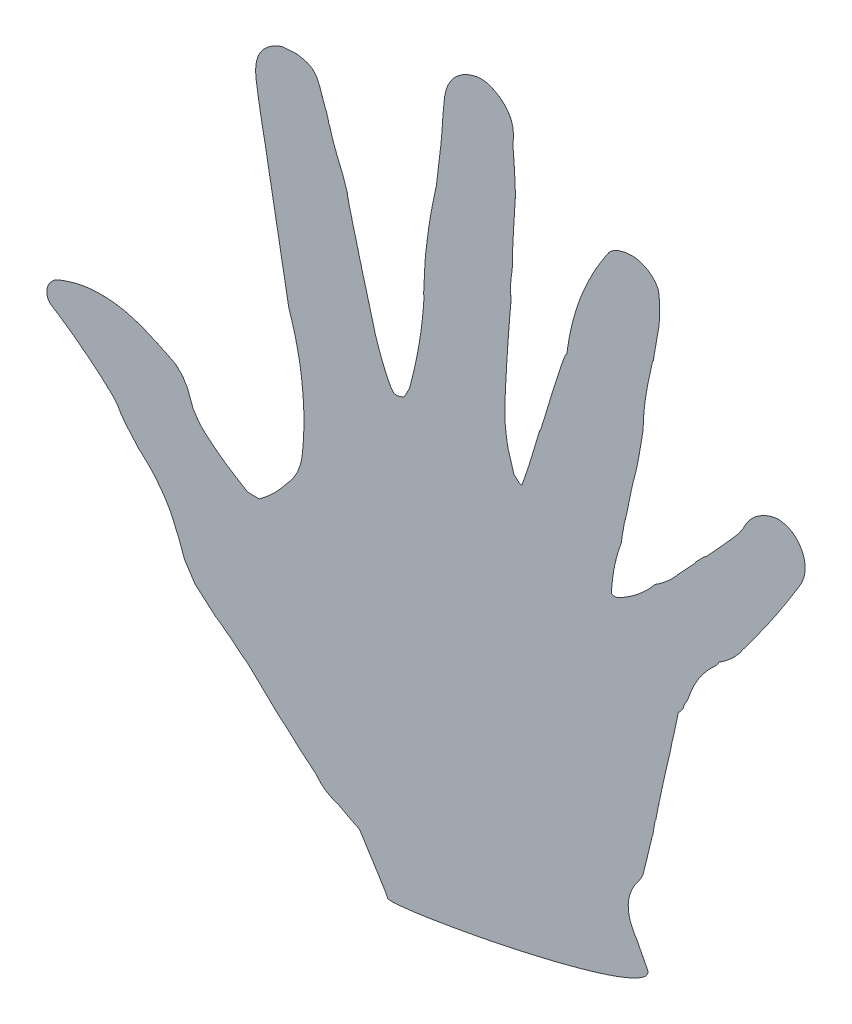
SolidWorks part; units mm, degrees
ref_plane "Plan de face" through (0, 0, 0) normal (0, 0, 1) x (1, 0, 0)
ref_plane "Plan de dessus" through (0, 0, 0) normal (0, 1, 0) x (1, 0, 0)
ref_plane "Plan de droite" through (0, 0, 0) normal (1, 0, 0) x (0, 0, -1)
sketch "Model" plane through (0, 0, 0) normal (0, 0, 1) x (1, 0, 0)
  line L0 (124.2622, -67.0317) -> (124.2391, -67.1279)
  line L1 (124.2391, -67.1279) -> (124.1933, -67.3399)
  line L2 (124.1933, -67.3399) -> (124.1478, -67.4942)
  line L3 (124.1478, -67.4942) -> (124.1478, -67.5328)
  line L4 (124.1478, -67.5328) -> (124.1247, -67.5707)
  line L5 (124.1247, -67.5707) -> (124.1247, -67.5907)
  line L6 (124.1247, -67.5907) -> (124.1023, -67.6102)
  line L7 (124.1023, -67.6102) -> (124.1247, -67.5707)
  line L8 (124.1247, -67.5707) -> (124.1247, -67.5523)
  line L9 (124.1247, -67.5523) -> (124.1478, -67.5137)
  line L10 (124.1478, -67.5137) -> (124.1478, -67.4942)
  line L11 (124.1478, -67.4942) -> (124.1478, -67.4364)
  line L12 (124.1478, -67.4364) -> (124.1933, -67.3399)
  line L13 (124.1933, -67.3399) -> (124.2167, -67.2626)
  line L14 (124.2167, -67.2626) -> (124.2622, -67.0317)
  line L15 (69.8453, -38.7148) -> (69.7992, -38.0785)
  line L16 (69.7992, -38.0785) -> (69.7308, -37.4801)
  line L17 (69.7308, -37.4801) -> (69.7075, -36.8825)
  line L18 (69.7075, -36.8825) -> (69.6846, -36.3227)
  line L19 (69.6846, -36.3227) -> (69.7075, -35.7444)
  line L20 (69.7075, -35.7444) -> (69.7308, -35.2046)
  line L21 (69.7308, -35.2046) -> (69.8453, -34.144)
  line L22 (69.8453, -34.144) -> (70.0743, -33.1213)
  line L23 (70.0743, -33.1213) -> (70.2345, -32.6199)
  line L24 (70.2345, -32.6199) -> (70.3719, -32.1567)
  line L25 (70.3719, -32.1567) -> (70.5781, -31.6746)
  line L26 (70.5781, -31.6746) -> (70.7841, -31.231)
  line L27 (70.7841, -31.231) -> (71.0134, -30.7874)
  line L28 (71.0134, -30.7874) -> (71.242, -30.3826)
  line L29 (71.242, -30.3826) -> (71.8378, -29.5525)
  line L30 (71.8378, -29.5525) -> (72.1586, -29.1476)
  line L31 (72.1586, -29.1476) -> (72.4791, -28.7814)
  line L32 (72.4791, -28.7814) -> (72.8681, -28.3957)
  line L33 (72.8681, -28.3957) -> (73.2345, -28.0481)
  line L34 (73.2345, -28.0481) -> (73.6467, -27.7008)
  line L35 (73.6467, -27.7008) -> (74.0594, -27.3926)
  line L36 (74.0594, -27.3926) -> (74.5402, -27.0642)
  line L37 (74.5402, -27.0642) -> (74.9984, -26.7748)
  line L38 (74.9984, -26.7748) -> (76.0059, -26.216)
  line L39 (76.0059, -26.216) -> (77.105, -25.6949)
  line L40 (77.105, -25.6949) -> (77.7009, -25.4439)
  line L41 (77.7009, -25.4439) -> (78.2731, -25.2319)
  line L42 (78.2731, -25.2319) -> (83.2661, -24.9425)
  line L43 (83.2661, -24.9425) -> (84.1592, -25.1163)
  line L44 (84.1592, -25.1163) -> (85.0982, -25.3282)
  line L45 (85.0982, -25.3282) -> (85.9915, -25.5602)
  line L46 (85.9915, -25.5602) -> (86.3808, -25.6758)
  line L47 (86.3808, -25.6758) -> (86.7015, -25.8103)
  line L48 (86.7015, -25.8103) -> (87.2737, -26.0425)
  line L49 (87.2737, -26.0425) -> (87.4806, -26.1579)
  line L50 (87.4806, -26.1579) -> (87.6405, -26.2928)
  line L51 (87.6405, -26.2928) -> (88.1672, -26.6015)
  line L52 (88.1672, -26.6015) -> (89.4498, -28.0681)
  line L53 (89.4498, -28.0681) -> (89.9077, -29.0511)
  line L54 (89.9077, -29.0511) -> (90.3891, -30.1315)
  line L55 (90.3891, -30.1315) -> (90.5952, -30.672)
  line L56 (90.5952, -30.672) -> (90.7783, -31.1926)
  line L57 (90.7783, -31.1926) -> (90.9612, -31.6746)
  line L58 (90.9612, -31.6746) -> (91.0988, -32.1376)
  line L59 (91.0988, -32.1376) -> (91.2589, -32.5611)
  line L60 (91.2589, -32.5611) -> (91.3963, -32.9668)
  line L61 (91.3963, -32.9668) -> (91.5341, -33.333)
  line L62 (91.5341, -33.333) -> (91.6256, -33.6806)
  line L63 (91.6256, -33.6806) -> (91.763, -33.9895)
  line L64 (91.763, -33.9895) -> (91.8547, -34.2787)
  line L65 (91.8547, -34.2787) -> (91.9463, -34.5297)
  line L66 (91.9463, -34.5297) -> (92.0147, -34.7607)
  line L67 (92.0147, -34.7607) -> (92.1064, -34.9539)
  line L68 (92.1064, -34.9539) -> (92.1753, -35.1274)
  line L69 (92.1753, -35.1274) -> (92.2209, -35.2618)
  line L70 (92.2209, -35.2618) -> (92.2438, -35.378)
  line L71 (92.2438, -35.378) -> (92.6562, -36.3811)
  line L72 (92.6562, -36.3811) -> (92.9768, -37.4036)
  line L73 (92.9768, -37.4036) -> (93.2515, -38.4445)
  line L74 (93.2515, -38.4445) -> (93.412, -39.5056)
  line L75 (93.412, -39.5056) -> (93.6411, -39.545)
  line L76 (93.6411, -39.545) -> (93.7097, -39.7759)
  line L77 (93.7097, -39.7759) -> (93.7783, -40.0651)
  line L78 (93.7783, -40.0651) -> (93.8702, -40.3732)
  line L79 (93.8702, -40.3732) -> (93.9388, -40.721)
  line L80 (93.9388, -40.721) -> (94.0535, -41.0679)
  line L81 (94.0535, -41.0679) -> (94.1679, -41.4543)
  line L82 (94.1679, -41.4543) -> (94.305, -41.8596)
  line L83 (94.305, -41.8596) -> (94.4196, -42.3218)
  line L84 (94.4196, -42.3218) -> (94.6032, -42.766)
  line L85 (94.6032, -42.766) -> (94.7634, -43.2671)
  line L86 (94.7634, -43.2671) -> (94.9463, -43.7689)
  line L87 (94.9463, -43.7689) -> (95.1299, -44.3275)
  line L88 (95.1299, -44.3275) -> (95.3587, -44.8875)
  line L89 (95.3587, -44.8875) -> (95.5647, -45.4849)
  line L90 (95.5647, -45.4849) -> (95.8169, -46.1033)
  line L91 (95.8169, -46.1033) -> (96.046, -46.7586)
  line L92 (96.046, -46.7586) -> (96.5729, -48.032)
  line L93 (96.5729, -48.032) -> (97.0764, -49.2857)
  line L94 (97.0764, -49.2857) -> (97.5801, -50.462)
  line L95 (97.5801, -50.462) -> (98.0615, -51.6194)
  line L96 (98.0615, -51.6194) -> (99.5727, -56.2298)
  line L97 (99.5727, -56.2298) -> (99.5498, -56.8275)
  line L98 (99.5498, -56.8275) -> (99.6875, -57.3095)
  line L99 (99.6875, -57.3095) -> (99.8249, -57.9076)
  line L100 (99.8249, -57.9076) -> (99.9166, -58.2355)
  line L101 (99.9166, -58.2355) -> (99.9849, -58.6014)
  line L102 (99.9849, -58.6014) -> (100.1687, -59.4124)
  line L103 (100.1687, -59.4124) -> (100.3973, -60.2804)
  line L104 (100.3973, -60.2804) -> (100.5348, -60.7432)
  line L105 (100.5348, -60.7432) -> (100.6493, -61.2638)
  line L106 (100.6493, -61.2638) -> (100.9239, -62.3442)
  line L107 (100.9239, -62.3442) -> (101.1993, -63.5401)
  line L108 (101.1993, -63.5401) -> (101.3823, -64.1385)
  line L109 (101.3823, -64.1385) -> (101.5423, -64.7938)
  line L110 (101.5423, -64.7938) -> (101.909, -66.1636)
  line L111 (101.909, -66.1636) -> (102.1152, -66.8576)
  line L112 (102.1152, -66.8576) -> (102.2981, -67.6102)
  line L113 (102.2981, -67.6102) -> (102.5043, -68.3619)
  line L114 (102.5043, -68.3619) -> (102.6873, -69.1722)
  line L115 (102.6873, -69.1722) -> (102.9165, -69.963)
  line L116 (102.9165, -69.963) -> (103.1226, -70.8115)
  line L117 (103.1226, -70.8115) -> (103.5809, -72.5671)
  line L118 (103.5809, -72.5671) -> (103.8331, -73.4541)
  line L119 (103.8331, -73.4541) -> (104.0617, -74.3998)
  line L120 (104.0617, -74.3998) -> (104.5659, -76.3473)
  line L121 (104.5659, -76.3473) -> (105.642, -80.2444)
  line L122 (105.642, -80.2444) -> (106.6726, -84.0629)
  line L123 (106.6726, -84.0629) -> (107.1766, -85.9346)
  line L124 (107.1766, -85.9346) -> (107.6804, -87.7859)
  line L125 (107.6804, -87.7859) -> (108.665, -91.4509)
  line L126 (108.665, -91.4509) -> (109.5125, -93.9584)
  line L127 (109.5125, -93.9584) -> (110.4291, -96.4661)
  line L128 (110.4291, -96.4661) -> (110.9328, -97.701)
  line L129 (110.9328, -97.701) -> (111.4364, -98.9547)
  line L130 (111.4364, -98.9547) -> (111.9863, -100.1891)
  line L131 (111.9863, -100.1891) -> (112.2608, -100.8059)
  line L132 (112.2608, -100.8059) -> (112.3987, -101.1146)
  line L133 (112.3987, -101.1146) -> (112.4669, -101.2693)
  line L134 (112.4669, -101.2693) -> (112.513, -101.4429)
  line L135 (112.513, -101.4429) -> (113.6813, -103.5065)
  line L136 (113.6813, -103.5065) -> (113.9787, -103.8924)
  line L137 (113.9787, -103.8924) -> (114.208, -104.2012)
  line L138 (114.208, -104.2012) -> (114.3227, -104.3161)
  line L139 (114.3227, -104.3161) -> (114.414, -104.4124)
  line L140 (114.414, -104.4124) -> (114.5057, -104.4904)
  line L141 (114.5057, -104.4904) -> (114.5511, -104.5488)
  line L142 (114.5511, -104.5488) -> (114.7801, -104.6253)
  line L143 (114.7801, -104.6253) -> (114.8493, -104.6253)
  line L144 (114.8493, -104.6253) -> (114.8948, -104.6453)
  line L145 (114.8948, -104.6453) -> (114.9864, -104.6832)
  line L146 (114.9864, -104.6832) -> (115.1239, -104.6832)
  line L147 (115.1239, -104.6832) -> (115.1925, -104.6832)
  line L148 (115.1925, -104.6832) -> (115.2386, -104.7023)
  line L149 (115.2386, -104.7023) -> (115.3757, -104.7023)
  line L150 (115.3757, -104.7023) -> (115.4446, -104.7023)
  line L151 (115.4446, -104.7023) -> (115.4901, -104.7216)
  line L152 (115.4901, -104.7216) -> (115.7883, -104.6832)
  line L153 (115.7883, -104.6832) -> (116.0629, -104.6453)
  line L154 (116.0629, -104.6453) -> (116.3836, -104.5673)
  line L155 (116.3836, -104.5673) -> (116.7042, -104.4708)
  line L156 (116.7042, -104.4708) -> (116.9334, -104.3745)
  line L157 (116.9334, -104.3745) -> (117.1394, -104.2975)
  line L158 (117.1394, -104.2975) -> (117.368, -104.1818)
  line L159 (117.368, -104.1818) -> (117.4373, -104.1432)
  line L160 (117.4373, -104.1432) -> (117.4826, -104.1235)
  line L161 (117.4826, -104.1235) -> (117.5747, -104.0853)
  line L162 (117.5747, -104.0853) -> (117.9179, -103.8924)
  line L163 (117.9179, -103.8924) -> (119.6127, -100.7675)
  line L164 (119.6127, -100.7675) -> (120.5749, -97.1026)
  line L165 (120.5749, -97.1026) -> (121.4224, -93.4763)
  line L166 (121.4224, -93.4763) -> (122.1782, -89.8495)
  line L167 (122.1782, -89.8495) -> (122.819, -86.2812)
  line L168 (122.819, -86.2812) -> (123.3689, -82.713)
  line L169 (123.3689, -82.713) -> (123.8042, -79.1835)
  line L170 (123.8042, -79.1835) -> (124.1478, -75.672)
  line L171 (124.1478, -75.672) -> (124.3767, -72.2004)
  line L172 (124.3767, -72.2004) -> (124.2167, -71.9691)
  line L173 (124.2167, -71.9691) -> (124.6749, -62.652)
  line L174 (124.6749, -62.652) -> (124.9261, -59.9135)
  line L175 (124.9261, -59.9135) -> (125.2242, -57.387)
  line L176 (125.2242, -57.387) -> (125.5448, -54.8795)
  line L177 (125.5448, -54.8795) -> (125.8879, -52.3722)
  line L178 (125.8879, -52.3722) -> (126.2776, -49.8831)
  line L179 (126.2776, -49.8831) -> (126.7127, -47.3756)
  line L180 (126.7127, -47.3756) -> (127.1943, -44.8875)
  line L181 (127.1943, -44.8875) -> (127.6976, -42.399)
  line L182 (127.6976, -42.399) -> (128.2247, -39.9306)
  line L183 (128.2247, -39.9306) -> (128.2706, -39.8722)
  line L184 (128.2706, -39.8722) -> (128.2706, -39.8143)
  line L185 (128.2706, -39.8143) -> (128.2929, -39.7759)
  line L186 (128.2929, -39.7759) -> (128.2929, -39.7567)
  line L187 (128.2929, -39.7567) -> (128.2929, -39.718)
  line L188 (128.2929, -39.718) -> (128.2929, -39.6021)
  line L189 (128.2929, -39.6021) -> (128.3395, -39.4486)
  line L190 (128.3395, -39.4486) -> (128.3618, -39.409)
  line L191 (128.3618, -39.409) -> (128.3618, -39.3902)
  line L192 (128.3618, -39.3902) -> (128.3618, -39.3521)
  line L193 (128.3618, -39.3521) -> (128.3618, -39.2743)
  line L194 (128.3618, -39.2743) -> (128.4073, -39.0624)
  line L195 (128.4073, -39.0624) -> (128.4073, -38.8302)
  line L196 (128.4073, -38.8302) -> (128.522, -37.9625)
  line L197 (128.522, -37.9625) -> (128.6137, -37.1908)
  line L198 (128.6137, -37.1908) -> (128.6595, -36.8446)
  line L199 (128.6595, -36.8446) -> (128.705, -36.4775)
  line L200 (128.705, -36.4775) -> (128.797, -35.7062)
  line L201 (128.797, -35.7062) -> (128.8424, -35.4745)
  line L202 (128.8424, -35.4745) -> (128.8659, -35.3584)
  line L203 (128.8659, -35.3584) -> (128.8659, -35.2618)
  line L204 (128.8659, -35.2618) -> (128.9117, -34.8189)
  line L205 (128.9117, -34.8189) -> (129.0033, -33.8928)
  line L206 (129.0033, -33.8928) -> (129.1408, -32.8509)
  line L207 (129.1408, -32.8509) -> (129.2093, -32.3114)
  line L208 (129.2093, -32.3114) -> (129.2555, -31.7517)
  line L209 (129.2555, -31.7517) -> (129.3465, -31.154)
  line L210 (129.3465, -31.154) -> (129.3926, -30.8453)
  line L211 (129.3926, -30.8453) -> (129.4154, -30.691)
  line L212 (129.4154, -30.691) -> (129.4154, -30.5556)
  line L213 (129.4154, -30.5556) -> (129.5525, -29.2825)
  line L214 (129.5525, -29.2825) -> (129.7137, -28.1061)
  line L215 (129.7137, -28.1061) -> (129.8284, -26.9875)
  line L216 (129.8284, -26.9875) -> (129.9421, -25.9266)
  line L217 (129.9421, -25.9266) -> (130.0338, -24.9234)
  line L218 (130.0338, -24.9234) -> (130.1254, -23.9395)
  line L219 (130.1254, -23.9395) -> (130.1936, -23.0334)
  line L220 (130.1936, -23.0334) -> (130.2628, -22.1652)
  line L221 (130.2628, -22.1652) -> (130.2859, -21.3551)
  line L222 (130.2859, -21.3551) -> (130.4461, -19.1756)
  line L223 (130.4461, -19.1756) -> (130.6294, -17.0152)
  line L224 (130.6294, -17.0152) -> (130.8354, -14.8551)
  line L225 (130.8354, -14.8551) -> (131.0876, -12.7136)
  line L226 (131.0876, -12.7136) -> (131.3167, -11.6329)
  line L227 (131.3167, -11.6329) -> (131.5913, -10.5723)
  line L228 (131.5913, -10.5723) -> (131.7749, -10.0326)
  line L229 (131.7749, -10.0326) -> (131.9802, -9.5307)
  line L230 (131.9802, -9.5307) -> (132.4384, -8.5278)
  line L231 (132.4384, -8.5278) -> (132.7819, -7.9299)
  line L232 (132.7819, -7.9299) -> (133.1488, -7.3704)
  line L233 (133.1488, -7.3704) -> (133.5378, -6.8302)
  line L234 (133.5378, -6.8302) -> (133.9271, -6.3483)
  line L235 (133.9271, -6.3483) -> (134.3849, -5.8463)
  line L236 (134.3849, -5.8463) -> (134.8434, -5.4038)
  line L237 (134.8434, -5.4038) -> (135.3247, -4.9783)
  line L238 (135.3247, -4.9783) -> (135.8053, -4.5925)
  line L239 (135.8053, -4.5925) -> (136.3552, -4.188)
  line L240 (136.3552, -4.188) -> (136.9043, -3.8408)
  line L241 (136.9043, -3.8408) -> (137.4769, -3.5126)
  line L242 (137.4769, -3.5126) -> (138.0729, -3.2234)
  line L243 (138.0729, -3.2234) -> (138.714, -2.934)
  line L244 (138.714, -2.934) -> (139.3782, -2.7032)
  line L245 (139.3782, -2.7032) -> (140.0652, -2.4707)
  line L246 (140.0652, -2.4707) -> (140.7518, -2.2977)
  line L247 (140.7518, -2.2977) -> (141.4846, -2.1244)
  line L248 (141.4846, -2.1244) -> (142.1949, -2.028)
  line L249 (142.1949, -2.028) -> (142.905, -1.9885)
  line L250 (142.905, -1.9885) -> (143.5919, -2.028)
  line L251 (143.5919, -2.028) -> (144.2792, -2.0848)
  line L252 (144.2792, -2.0848) -> (144.9434, -2.2397)
  line L253 (144.9434, -2.2397) -> (145.6073, -2.4324)
  line L254 (145.6073, -2.4324) -> (146.2488, -2.7032)
  line L255 (146.2488, -2.7032) -> (147.2792, -3.1654)
  line L256 (147.2792, -3.1654) -> (148.1953, -3.6863)
  line L257 (148.1953, -3.6863) -> (149.0428, -4.2463)
  line L258 (149.0428, -4.2463) -> (149.799, -4.8436)
  line L259 (149.799, -4.8436) -> (150.5086, -5.4801)
  line L260 (150.5086, -5.4801) -> (151.1274, -6.1554)
  line L261 (151.1274, -6.1554) -> (151.6765, -6.869)
  line L262 (151.6765, -6.869) -> (152.1347, -7.6602)
  line L263 (152.1347, -7.6602) -> (152.5468, -8.4505)
  line L264 (152.5468, -8.4505) -> (152.7307, -8.856)
  line L265 (152.7307, -8.856) -> (152.8678, -9.2995)
  line L266 (152.8678, -9.2995) -> (153.1193, -10.1677)
  line L267 (153.1193, -10.1677) -> (153.2568, -11.1127)
  line L268 (153.2568, -11.1127) -> (153.3712, -12.0582)
  line L269 (153.3712, -12.0582) -> (153.3712, -13.0795)
  line L270 (153.3712, -13.0795) -> (153.3712, -13.5813)
  line L271 (153.3712, -13.5813) -> (153.3254, -14.1218)
  line L272 (153.3254, -14.1218) -> (153.1655, -15.2211)
  line L273 (153.1655, -15.2211) -> (153.4401, -18.191)
  line L274 (153.4401, -18.191) -> (153.6468, -21.162)
  line L275 (153.6468, -21.162) -> (153.8297, -24.0938)
  line L276 (153.8297, -24.0938) -> (153.9437, -27.007)
  line L277 (153.9437, -27.007) -> (154.0126, -28.4341)
  line L278 (154.0126, -28.4341) -> (153.9903, -29.8809)
  line L279 (153.9903, -29.8809) -> (153.9214, -31.3275)
  line L280 (153.9214, -31.3275) -> (153.8066, -32.794)
  line L281 (153.8066, -32.794) -> (153.7153, -34.3171)
  line L282 (153.7153, -34.3171) -> (153.623, -35.9182)
  line L283 (153.623, -35.9182) -> (153.5321, -37.5763)
  line L284 (153.5321, -37.5763) -> (153.3943, -39.3321)
  line L285 (153.3943, -39.3321) -> (153.3712, -40.1805)
  line L286 (153.3712, -40.1805) -> (153.3254, -41.0108)
  line L287 (153.3254, -41.0108) -> (153.2802, -41.8202)
  line L288 (153.2802, -41.8202) -> (153.2337, -42.6115)
  line L289 (153.2337, -42.6115) -> (153.211, -43.3445)
  line L290 (153.211, -43.3445) -> (153.1655, -44.0776)
  line L291 (153.1655, -44.0776) -> (153.1424, -44.7716)
  line L292 (153.1424, -44.7716) -> (153.0963, -45.447)
  line L293 (153.0963, -45.447) -> (153.0963, -46.064)
  line L294 (153.0963, -46.064) -> (153.0745, -46.6816)
  line L295 (153.0745, -46.6816) -> (153.0745, -47.2605)
  line L296 (153.0745, -47.2605) -> (153.0277, -47.8195)
  line L297 (153.0277, -47.8195) -> (153.0277, -48.34)
  line L298 (153.0277, -48.34) -> (153.0277, -48.8415)
  line L299 (153.0277, -48.8415) -> (153.0277, -49.3047)
  line L300 (153.0277, -49.3047) -> (153.0277, -49.517)
  line L301 (153.0277, -49.517) -> (153.0046, -49.7482)
  line L302 (153.0046, -49.7482) -> (153.0046, -49.8831)
  line L303 (153.0046, -49.8831) -> (153.0046, -50.0953)
  line L304 (153.0046, -50.0953) -> (152.9822, -50.3657)
  line L305 (152.9822, -50.3657) -> (152.9364, -50.7323)
  line L306 (152.9364, -50.7323) -> (152.8902, -51.1183)
  line L307 (152.8902, -51.1183) -> (152.8451, -51.6005)
  line L308 (152.8451, -51.6005) -> (152.7762, -52.121)
  line L309 (152.7762, -52.121) -> (152.6842, -52.7379)
  line L310 (152.6842, -52.7379) -> (152.6387, -53.3365)
  line L311 (152.6387, -53.3365) -> (152.616, -53.606)
  line L312 (152.616, -53.606) -> (152.5702, -53.8758)
  line L313 (152.5702, -53.8758) -> (152.5237, -54.3579)
  line L314 (152.5237, -54.3579) -> (152.5237, -54.4544)
  line L315 (152.5237, -54.4544) -> (152.5016, -54.5705)
  line L316 (152.5016, -54.5705) -> (152.4555, -54.802)
  line L317 (152.4555, -54.802) -> (152.4555, -54.9761)
  line L318 (152.4555, -54.9761) -> (152.4327, -55.1689)
  line L319 (152.4327, -55.1689) -> (152.3869, -55.4772)
  line L320 (152.3869, -55.4772) -> (152.3869, -55.728)
  line L321 (152.3869, -55.728) -> (152.3869, -55.8245)
  line L322 (152.3869, -55.8245) -> (152.3642, -55.9404)
  line L323 (152.3642, -55.9404) -> (152.3642, -55.9974)
  line L324 (152.3642, -55.9974) -> (152.5016, -57.6182)
  line L325 (152.5016, -57.6182) -> (152.5468, -59.2577)
  line L326 (152.5468, -59.2577) -> (152.5016, -60.8971)
  line L327 (152.5016, -60.8971) -> (152.3411, -62.5555)
  line L328 (152.3411, -62.5555) -> (152.2949, -63.2308)
  line L329 (152.2949, -63.2308) -> (152.2036, -63.9837)
  line L330 (152.2036, -63.9837) -> (152.1578, -64.755)
  line L331 (152.1578, -64.755) -> (152.0662, -65.585)
  line L332 (152.0662, -65.585) -> (152.02, -66.4332)
  line L333 (152.02, -66.4332) -> (151.9291, -67.3399)
  line L334 (151.9291, -67.3399) -> (151.8598, -68.2854)
  line L335 (151.8598, -68.2854) -> (151.7682, -69.2881)
  line L336 (151.7682, -69.2881) -> (151.7227, -70.3104)
  line L337 (151.7227, -70.3104) -> (151.6307, -71.3717)
  line L338 (151.6307, -71.3717) -> (151.5618, -72.4705)
  line L339 (151.5618, -72.4705) -> (151.4709, -73.647)
  line L340 (151.4709, -73.647) -> (151.4243, -74.8239)
  line L341 (151.4243, -74.8239) -> (151.3327, -76.0775)
  line L342 (151.3327, -76.0775) -> (151.2421, -77.3514)
  line L343 (151.2421, -77.3514) -> (151.1501, -78.6817)
  line L344 (151.1501, -78.6817) -> (151.104, -79.9934)
  line L345 (151.104, -79.9934) -> (151.013, -81.2856)
  line L346 (151.013, -81.2856) -> (150.9665, -82.5395)
  line L347 (150.9665, -82.5395) -> (150.8755, -83.7932)
  line L348 (150.8755, -83.7932) -> (150.829, -84.989)
  line L349 (150.829, -84.989) -> (150.806, -85.5681)
  line L350 (150.806, -85.5681) -> (150.7605, -86.166)
  line L351 (150.7605, -86.166) -> (150.7147, -87.3041)
  line L352 (150.7147, -87.3041) -> (150.7147, -87.5745)
  line L353 (150.7147, -87.5745) -> (150.7147, -87.7089)
  line L354 (150.7147, -87.7089) -> (150.6916, -87.8637)
  line L355 (150.6916, -87.8637) -> (150.6461, -88.4421)
  line L356 (150.6461, -88.4421) -> (150.623, -89.2905)
  line L357 (150.623, -89.2905) -> (150.623, -89.7149)
  line L358 (150.623, -89.7149) -> (150.623, -89.9273)
  line L359 (150.623, -89.9273) -> (150.5996, -90.1587)
  line L360 (150.5996, -90.1587) -> (150.5775, -91.8561)
  line L361 (150.5775, -91.8561) -> (150.623, -92.6855)
  line L362 (150.623, -92.6855) -> (150.6461, -93.5345)
  line L363 (150.6461, -93.5345) -> (150.7147, -95.1932)
  line L364 (150.7147, -95.1932) -> (150.8979, -96.8132)
  line L365 (150.8979, -96.8132) -> (151.104, -98.4725)
  line L366 (151.104, -98.4725) -> (151.3789, -100.1312)
  line L367 (151.3789, -100.1312) -> (151.7003, -101.8284)
  line L368 (151.7003, -101.8284) -> (151.8825, -102.3304)
  line L369 (151.8825, -102.3304) -> (153.5548, -107.9242)
  line L370 (153.5548, -107.9242) -> (155.5471, -109.6405)
  line L371 (155.5471, -109.6405) -> (155.7989, -109.66)
  line L372 (155.7989, -109.66) -> (155.9595, -109.6405)
  line L373 (155.9595, -109.6405) -> (156.0738, -109.5826)
  line L374 (156.0738, -109.5826) -> (156.1424, -109.5055)
  line L375 (156.1424, -109.5055) -> (156.3264, -109.0621)
  line L376 (156.3264, -109.0621) -> (156.4862, -108.5994)
  line L377 (156.4862, -108.5994) -> (156.6692, -108.0775)
  line L378 (156.6692, -108.0775) -> (156.8535, -107.5574)
  line L379 (156.8535, -107.5574) -> (157.0819, -106.9787)
  line L380 (157.0819, -106.9787) -> (157.2652, -106.3811)
  line L381 (157.2652, -106.3811) -> (157.4943, -105.7443)
  line L382 (157.4943, -105.7443) -> (157.7006, -105.0878)
  line L383 (157.7006, -105.0878) -> (157.8374, -104.7216)
  line L384 (157.8374, -104.7216) -> (157.9518, -104.3745)
  line L385 (157.9518, -104.3745) -> (158.1812, -103.6223)
  line L386 (158.1812, -103.6223) -> (158.4561, -102.8314)
  line L387 (158.4561, -102.8314) -> (158.6852, -102.0413)
  line L388 (158.6852, -102.0413) -> (158.9598, -101.1919)
  line L389 (158.9598, -101.1919) -> (159.2347, -100.3238)
  line L390 (159.2347, -100.3238) -> (159.5093, -99.4172)
  line L391 (159.5093, -99.4172) -> (159.7842, -98.4725)
  line L392 (159.7842, -98.4725) -> (161.8919, -91.4318)
  line L393 (161.8919, -91.4318) -> (162.1203, -91.3353)
  line L394 (162.1203, -91.3353) -> (162.7846, -89.2138)
  line L395 (162.7846, -89.2138) -> (163.4026, -87.2269)
  line L396 (163.4026, -87.2269) -> (163.9986, -85.3168)
  line L397 (163.9986, -85.3168) -> (164.5254, -83.5234)
  line L398 (164.5254, -83.5234) -> (165.0514, -81.8065)
  line L399 (165.0514, -81.8065) -> (165.5327, -80.2246)
  line L400 (165.5327, -80.2246) -> (165.9909, -78.7201)
  line L401 (165.9909, -78.7201) -> (166.4033, -77.3314)
  line L402 (166.4033, -77.3314) -> (166.8163, -76.0775)
  line L403 (166.8163, -76.0775) -> (167.1815, -74.9201)
  line L404 (167.1815, -74.9201) -> (167.5484, -73.8208)
  line L405 (167.5484, -73.8208) -> (167.8695, -72.7987)
  line L406 (167.8695, -72.7987) -> (168.1896, -71.8146)
  line L407 (168.1896, -71.8146) -> (168.4876, -70.9275)
  line L408 (168.4876, -70.9275) -> (168.7625, -70.0982)
  line L409 (168.7625, -70.0982) -> (169.014, -69.3465)
  line L410 (169.014, -69.3465) -> (169.2658, -68.6316)
  line L411 (169.2658, -68.6316) -> (169.4953, -67.9962)
  line L412 (169.4953, -67.9962) -> (169.7013, -67.4172)
  line L413 (169.7013, -67.4172) -> (169.8842, -66.9353)
  line L414 (169.8842, -66.9353) -> (170.0678, -66.4719)
  line L415 (170.0678, -66.4719) -> (170.2277, -66.1052)
  line L416 (170.2277, -66.1052) -> (170.3658, -65.7968)
  line L417 (170.3658, -65.7968) -> (170.4806, -65.585)
  line L418 (170.4806, -65.585) -> (170.7314, -65.4492)
  line L419 (170.7314, -65.4492) -> (171.0752, -63.0382)
  line L420 (171.0752, -63.0382) -> (171.4645, -60.6854)
  line L421 (171.4645, -60.6854) -> (171.9457, -58.332)
  line L422 (171.9457, -58.332) -> (172.4725, -56.0365)
  line L423 (172.4725, -56.0365) -> (173.0909, -53.7409)
  line L424 (173.0909, -53.7409) -> (173.7551, -51.4842)
  line L425 (173.7551, -51.4842) -> (174.5106, -49.2278)
  line L426 (174.5106, -49.2278) -> (175.3126, -47.0283)
  line L427 (175.3126, -47.0283) -> (176.2283, -44.81)
  line L428 (176.2283, -44.81) -> (177.1902, -42.6501)
  line L429 (177.1902, -42.6501) -> (178.221, -40.4897)
  line L430 (178.221, -40.4897) -> (179.2983, -38.3877)
  line L431 (179.2983, -38.3877) -> (180.4651, -36.2844)
  line L432 (180.4651, -36.2844) -> (181.7026, -34.2205)
  line L433 (181.7026, -34.2205) -> (183.0076, -32.1567)
  line L434 (183.0076, -32.1567) -> (184.3584, -30.1506)
  line L435 (184.3584, -30.1506) -> (184.7946, -29.6681)
  line L436 (184.7946, -29.6681) -> (185.2528, -29.2633)
  line L437 (185.2528, -29.2633) -> (185.7561, -28.8969)
  line L438 (185.7561, -28.8969) -> (186.2832, -28.5691)
  line L439 (186.2832, -28.5691) -> (186.8558, -28.2799)
  line L440 (186.8558, -28.2799) -> (187.4738, -28.0288)
  line L441 (187.4738, -28.0288) -> (188.1153, -27.8167)
  line L442 (188.1153, -27.8167) -> (188.7788, -27.6429)
  line L443 (188.7788, -27.6429) -> (189.6725, -27.45)
  line L444 (189.6725, -27.45) -> (190.52, -27.3348)
  line L445 (190.52, -27.3348) -> (191.3671, -27.2767)
  line L446 (191.3671, -27.2767) -> (192.1457, -27.2767)
  line L447 (192.1457, -27.2767) -> (192.9474, -27.3151)
  line L448 (192.9474, -27.3151) -> (193.6798, -27.4312)
  line L449 (193.6798, -27.4312) -> (194.4133, -27.5859)
  line L450 (194.4133, -27.5859) -> (195.1009, -27.8167)
  line L451 (195.1009, -27.8167) -> (195.8103, -28.0681)
  line L452 (195.8103, -28.0681) -> (196.4517, -28.3957)
  line L453 (196.4517, -28.3957) -> (197.0925, -28.7617)
  line L454 (197.0925, -28.7617) -> (197.6882, -29.2055)
  line L455 (197.6882, -29.2055) -> (198.2842, -29.6881)
  line L456 (198.2842, -29.6881) -> (198.8337, -30.2278)
  line L457 (198.8337, -30.2278) -> (199.3832, -30.8255)
  line L458 (199.3832, -30.8255) -> (199.8638, -31.5007)
  line L459 (199.8638, -31.5007) -> (200.3223, -32.2917)
  line L460 (200.3223, -32.2917) -> (200.4598, -32.8319)
  line L461 (200.4598, -32.8319) -> (200.5745, -33.4688)
  line L462 (200.5745, -33.4688) -> (200.6658, -34.144)
  line L463 (200.6658, -34.144) -> (200.7343, -34.9155)
  line L464 (200.7343, -34.9155) -> (200.8032, -35.7251)
  line L465 (200.8032, -35.7251) -> (200.8263, -36.6317)
  line L466 (200.8263, -36.6317) -> (200.8491, -37.5963)
  line L467 (200.8491, -37.5963) -> (200.8263, -38.6374)
  line L468 (200.8263, -38.6374) -> (200.8263, -39.6603)
  line L469 (200.8263, -39.6603) -> (200.7802, -40.6632)
  line L470 (200.7802, -40.6632) -> (200.7343, -41.589)
  line L471 (200.7343, -41.589) -> (200.6658, -42.4953)
  line L472 (200.6658, -42.4953) -> (198.7651, -53.4712)
  line L473 (198.7651, -53.4712) -> (198.5588, -53.5866)
  line L474 (198.5588, -53.5866) -> (198.238, -55.0912)
  line L475 (198.238, -55.0912) -> (197.9173, -56.5571)
  line L476 (197.9173, -56.5571) -> (197.7798, -57.2511)
  line L477 (197.7798, -57.2511) -> (197.7113, -57.5987)
  line L478 (197.7113, -57.5987) -> (197.6203, -57.9658)
  line L479 (197.6203, -57.9658) -> (197.4822, -58.6407)
  line L480 (197.4822, -58.6407) -> (197.4591, -58.7947)
  line L481 (197.4591, -58.7947) -> (197.4136, -58.9685)
  line L482 (197.4136, -58.9685) -> (197.322, -59.3161)
  line L483 (197.322, -59.3161) -> (197.2765, -59.6244)
  line L484 (197.2765, -59.6244) -> (197.2527, -59.7786)
  line L485 (197.2527, -59.7786) -> (197.2076, -59.9514)
  line L486 (197.2076, -59.9514) -> (197.0701, -60.5889)
  line L487 (197.0701, -60.5889) -> (196.8407, -61.8038)
  line L488 (196.8407, -61.8038) -> (196.7491, -62.3826)
  line L489 (196.7491, -62.3826) -> (196.6347, -62.9612)
  line L490 (196.6347, -62.9612) -> (196.543, -63.5202)
  line L491 (196.543, -63.5202) -> (196.4976, -63.7909)
  line L492 (196.4976, -63.7909) -> (196.4976, -63.8488)
  line L493 (196.4976, -63.8488) -> (196.4748, -63.9256)
  line L494 (196.4748, -63.9256) -> (196.4287, -64.08)
  line L495 (196.4287, -64.08) -> (196.2226, -65.4689)
  line L496 (196.2226, -65.4689) -> (196.039, -66.8388)
  line L497 (196.039, -66.8388) -> (195.9708, -67.4942)
  line L498 (195.9708, -67.4942) -> (195.8785, -68.1691)
  line L499 (195.8785, -68.1691) -> (195.7417, -69.4998)
  line L500 (195.7417, -69.4998) -> (195.6501, -70.7731)
  line L501 (195.6501, -70.7731) -> (195.627, -71.3905)
  line L502 (195.627, -71.3905) -> (195.5815, -72.027)
  line L503 (195.5815, -72.027) -> (195.5354, -73.2424)
  line L504 (195.5354, -73.2424) -> (195.5354, -73.8398)
  line L505 (195.5354, -73.8398) -> (195.5126, -74.4576)
  line L506 (195.5126, -74.4576) -> (194.4822, -80.4945)
  line L507 (194.4822, -80.4945) -> (194.3447, -81.3055)
  line L508 (194.3447, -81.3055) -> (194.2069, -82.0959)
  line L509 (194.2069, -82.0959) -> (194.0702, -82.8485)
  line L510 (194.0702, -82.8485) -> (194.0702, -82.925)
  line L511 (194.0702, -82.925) -> (194.0467, -83.022)
  line L512 (194.0467, -83.022) -> (194.0009, -83.2147)
  line L513 (194.0009, -83.2147) -> (193.9093, -83.6002)
  line L514 (193.9093, -83.6002) -> (193.7722, -84.3142)
  line L515 (193.7722, -84.3142) -> (193.6347, -85.0086)
  line L516 (193.6347, -85.0086) -> (193.4976, -85.6644)
  line L517 (193.4976, -85.6644) -> (193.4283, -85.973)
  line L518 (193.4283, -85.973) -> (193.3367, -86.3007)
  line L519 (193.3367, -86.3007) -> (193.2909, -86.5901)
  line L520 (193.2909, -86.5901) -> (193.2223, -86.8991)
  line L521 (193.2223, -86.8991) -> (193.0849, -87.4777)
  line L522 (193.0849, -87.4777) -> (192.8106, -88.5577)
  line L523 (192.8106, -88.5577) -> (192.7186, -89.0592)
  line L524 (192.7186, -89.0592) -> (192.5815, -89.5411)
  line L525 (192.5815, -89.5411) -> (192.5354, -89.753)
  line L526 (192.5354, -89.753) -> (192.4671, -89.9854)
  line L527 (192.4671, -89.9854) -> (192.3287, -90.4286)
  line L528 (192.3287, -90.4286) -> (192.2143, -90.9686)
  line L529 (192.2143, -90.9686) -> (192.0541, -91.5856)
  line L530 (192.0541, -91.5856) -> (191.8942, -92.3)
  line L531 (191.8942, -92.3) -> (191.7106, -93.1099)
  line L532 (191.7106, -93.1099) -> (191.5273, -93.9781)
  line L533 (191.5273, -93.9781) -> (191.322, -94.942)
  line L534 (191.322, -94.942) -> (191.1156, -96.0029)
  line L535 (191.1156, -96.0029) -> (190.8635, -97.1605)
  line L536 (190.8635, -97.1605) -> (190.6802, -98.1833)
  line L537 (190.6802, -98.1833) -> (190.5885, -98.6655)
  line L538 (190.5885, -98.6655) -> (190.4742, -99.1666)
  line L539 (190.4742, -99.1666) -> (190.2912, -100.0926)
  line L540 (190.2912, -100.0926) -> (190.1992, -100.5167)
  line L541 (190.1992, -100.5167) -> (190.1531, -100.7289)
  line L542 (190.1531, -100.7289) -> (190.0845, -100.9602)
  line L543 (190.0845, -100.9602) -> (189.9012, -101.7516)
  line L544 (189.9012, -101.7516) -> (189.7183, -102.5033)
  line L545 (189.7183, -102.5033) -> (189.535, -103.198)
  line L546 (189.535, -103.198) -> (189.4434, -103.5065)
  line L547 (189.4434, -103.5065) -> (189.3976, -103.6607)
  line L548 (189.3976, -103.6607) -> (189.3748, -103.7375)
  line L549 (189.3748, -103.7375) -> (189.329, -103.8341)
  line L550 (189.329, -103.8341) -> (189.2828, -104.2197)
  line L551 (189.2828, -104.2197) -> (189.237, -104.5867)
  line L552 (189.237, -104.5867) -> (189.1916, -104.8951)
  line L553 (189.1916, -104.8951) -> (189.1464, -105.1653)
  line L554 (189.1464, -105.1653) -> (189.1464, -105.3581)
  line L555 (189.1464, -105.3581) -> (189.0996, -105.5317)
  line L556 (189.0996, -105.5317) -> (189.0996, -105.6476)
  line L557 (189.0996, -105.6476) -> (189.0544, -105.7443)
  line L558 (189.0544, -105.7443) -> (189.0083, -105.9176)
  line L559 (189.0083, -105.9176) -> (188.9621, -106.1298)
  line L560 (188.9621, -106.1298) -> (188.9173, -106.3811)
  line L561 (188.9173, -106.3811) -> (188.8481, -106.6701)
  line L562 (188.8481, -106.6701) -> (188.8026, -106.9595)
  line L563 (188.8026, -106.9595) -> (188.7561, -107.3257)
  line L564 (188.7561, -107.3257) -> (188.619, -108.1167)
  line L565 (188.619, -108.1167) -> (188.5277, -108.9267)
  line L566 (188.5277, -108.9267) -> (188.4354, -109.6787)
  line L567 (188.4354, -109.6787) -> (187.7946, -111.5117)
  line L568 (187.7946, -111.5117) -> (187.1993, -113.3819)
  line L569 (187.1993, -113.3819) -> (186.6952, -115.292)
  line L570 (186.6952, -115.292) -> (186.2367, -117.2793)
  line L571 (186.2367, -117.2793) -> (185.8705, -119.2652)
  line L572 (185.8705, -119.2652) -> (185.5728, -121.3103)
  line L573 (185.5728, -121.3103) -> (185.3437, -123.3742)
  line L574 (185.3437, -123.3742) -> (185.1832, -125.5152)
  line L575 (185.1832, -125.5152) -> (185.5039, -125.8235)
  line L576 (185.5039, -125.8235) -> (186.5126, -125.901)
  line L577 (186.5126, -125.901) -> (187.4049, -125.6702)
  line L578 (187.4049, -125.6702) -> (188.2982, -125.1682)
  line L579 (188.2982, -125.1682) -> (189.1464, -124.6856)
  line L580 (189.1464, -124.6856) -> (190.8176, -123.6445)
  line L581 (190.8176, -123.6445) -> (191.642, -123.0848)
  line L582 (191.642, -123.0848) -> (192.4206, -122.5257)
  line L583 (192.4206, -122.5257) -> (193.1992, -121.9276)
  line L584 (193.1992, -121.9276) -> (193.9323, -121.3488)
  line L585 (193.9323, -121.3488) -> (195.421, -120.0759)
  line L586 (195.421, -120.0759) -> (196.8183, -118.7642)
  line L587 (196.8183, -118.7642) -> (197.5059, -118.07)
  line L588 (197.5059, -118.07) -> (198.1467, -117.3756)
  line L589 (198.1467, -117.3756) -> (199.4059, -115.9288)
  line L590 (199.4059, -115.9288) -> (200.5049, -115.2147)
  line L591 (200.5049, -115.2147) -> (201.5364, -114.4628)
  line L592 (201.5364, -114.4628) -> (202.5206, -113.6911)
  line L593 (202.5206, -113.6911) -> (203.4604, -112.8999)
  line L594 (203.4604, -112.8999) -> (204.3989, -112.0516)
  line L595 (204.3989, -112.0516) -> (205.246, -111.1834)
  line L596 (205.246, -111.1834) -> (206.0939, -110.2959)
  line L597 (206.0939, -110.2959) -> (206.8494, -109.3899)
  line L598 (206.8494, -109.3899) -> (212.438, -103.4099)
  line L599 (212.438, -103.4099) -> (212.438, -103.1401)
  line L600 (212.438, -103.1401) -> (215.5066, -100.0347)
  line L601 (215.5066, -100.0347) -> (215.8042, -99.9762)
  line L602 (215.8042, -99.9762) -> (218.3471, -97.2378)
  line L603 (218.3471, -97.2378) -> (220.8664, -94.4792)
  line L604 (220.8664, -94.4792) -> (223.3858, -91.6823)
  line L605 (223.3858, -91.6823) -> (225.8591, -88.8664)
  line L606 (225.8591, -88.8664) -> (226.2939, -88.3264)
  line L607 (226.2939, -88.3264) -> (226.6835, -87.8055)
  line L608 (226.6835, -87.8055) -> (227.0728, -87.2653)
  line L609 (227.0728, -87.2653) -> (227.3942, -86.7253)
  line L610 (227.3942, -86.7253) -> (227.6226, -86.455)
  line L611 (227.6226, -86.455) -> (227.8059, -86.1849)
  line L612 (227.8059, -86.1849) -> (227.9885, -85.8954)
  line L613 (227.9885, -85.8954) -> (228.1263, -85.626)
  line L614 (228.1263, -85.626) -> (228.5153, -84.8737)
  line L615 (228.5153, -84.8737) -> (228.9049, -84.1987)
  line L616 (228.9049, -84.1987) -> (229.3404, -83.5234)
  line L617 (229.3404, -83.5234) -> (229.7751, -82.9055)
  line L618 (229.7751, -82.9055) -> (230.2561, -82.308)
  line L619 (230.2561, -82.308) -> (230.7601, -81.7483)
  line L620 (230.7601, -81.7483) -> (231.3099, -81.2092)
  line L621 (231.3099, -81.2092) -> (231.8597, -80.7267)
  line L622 (231.8597, -80.7267) -> (232.4775, -80.2444)
  line L623 (232.4775, -80.2444) -> (233.0965, -79.8196)
  line L624 (233.0965, -79.8196) -> (233.7604, -79.415)
  line L625 (233.7604, -79.415) -> (234.4243, -79.0479)
  line L626 (234.4243, -79.0479) -> (235.1571, -78.6817)
  line L627 (235.1571, -78.6817) -> (235.8905, -78.3923)
  line L628 (235.8905, -78.3923) -> (236.6691, -78.1032)
  line L629 (236.6691, -78.1032) -> (237.4477, -77.8903)
  line L630 (237.4477, -77.8903) -> (238.3179, -77.6976)
  line L631 (238.3179, -77.6976) -> (239.142, -77.6206)
  line L632 (239.142, -77.6206) -> (239.9667, -77.6404)
  line L633 (239.9667, -77.6404) -> (240.7918, -77.7749)
  line L634 (240.7918, -77.7749) -> (241.5246, -77.9298)
  line L635 (241.5246, -77.9298) -> (242.1885, -78.1415)
  line L636 (242.1885, -78.1415) -> (242.853, -78.3923)
  line L637 (242.853, -78.3923) -> (243.4484, -78.7201)
  line L638 (243.4484, -78.7201) -> (244.0437, -79.0677)
  line L639 (244.0437, -79.0677) -> (244.5708, -79.4728)
  line L640 (244.5708, -79.4728) -> (245.0965, -79.9161)
  line L641 (245.0965, -79.9161) -> (245.555, -80.4178)
  line L642 (245.555, -80.4178) -> (246.3336, -81.3625)
  line L643 (246.3336, -81.3625) -> (246.952, -82.385)
  line L644 (246.952, -82.385) -> (247.3868, -83.2726)
  line L645 (247.3868, -83.2726) -> (247.6851, -84.2178)
  line L646 (247.6851, -84.2178) -> (247.9597, -85.2978)
  line L647 (247.9597, -85.2978) -> (248.0517, -85.8382)
  line L648 (248.0517, -85.8382) -> (248.0741, -86.3971)
  line L649 (248.0741, -86.3971) -> (248.0972, -87.4777)
  line L650 (248.0972, -87.4777) -> (248.0517, -88.0172)
  line L651 (248.0517, -88.0172) -> (247.9597, -88.577)
  line L652 (247.9597, -88.577) -> (247.754, -89.6565)
  line L653 (247.754, -89.6565) -> (247.3868, -90.7369)
  line L654 (247.3868, -90.7369) -> (247.1811, -91.258)
  line L655 (247.1811, -91.258) -> (246.9286, -91.7982)
  line L656 (246.9286, -91.7982) -> (246.3109, -92.8787)
  line L657 (246.3109, -92.8787) -> (243.9748, -96.659)
  line L658 (243.9748, -96.659) -> (242.83, -98.5106)
  line L659 (242.83, -98.5106) -> (241.639, -100.3432)
  line L660 (241.639, -100.3432) -> (239.3032, -103.9306)
  line L661 (239.3032, -103.9306) -> (239.028, -104.3556)
  line L662 (239.028, -104.3556) -> (238.8905, -104.5673)
  line L663 (238.8905, -104.5673) -> (238.7306, -104.7988)
  line L664 (238.7306, -104.7988) -> (238.1343, -105.6862)
  line L665 (238.1343, -105.6862) -> (236.9437, -107.422)
  line L666 (236.9437, -107.422) -> (235.7989, -109.1194)
  line L667 (235.7989, -109.1194) -> (234.6082, -110.7977)
  line L668 (234.6082, -110.7977) -> (232.2718, -114.0768)
  line L669 (232.2718, -114.0768) -> (231.1263, -115.6775)
  line L670 (231.1263, -115.6775) -> (229.936, -117.2597)
  line L671 (229.936, -117.2597) -> (228.7905, -118.822)
  line L672 (228.7905, -118.822) -> (227.5992, -120.3656)
  line L673 (227.5992, -120.3656) -> (227.2554, -120.9821)
  line L674 (227.2554, -120.9821) -> (226.523, -121.8889)
  line L675 (226.523, -121.8889) -> (225.7216, -122.7954)
  line L676 (225.7216, -122.7954) -> (224.9199, -123.6636)
  line L677 (224.9199, -123.6636) -> (224.0266, -124.4927)
  line L678 (224.0266, -124.4927) -> (223.1333, -125.284)
  line L679 (223.1333, -125.284) -> (222.1718, -126.0361)
  line L680 (222.1718, -126.0361) -> (221.1865, -126.7495)
  line L681 (221.1865, -126.7495) -> (220.133, -127.4441)
  line L682 (220.133, -127.4441) -> (219.8815, -127.9071)
  line L683 (219.8815, -127.9071) -> (219.5832, -128.3701)
  line L684 (219.5832, -128.3701) -> (219.2397, -128.7942)
  line L685 (219.2397, -128.7942) -> (218.8052, -129.2186)
  line L686 (218.8052, -129.2186) -> (218.14, -129.8363)
  line L687 (218.14, -129.8363) -> (217.4768, -130.4919)
  line L688 (217.4768, -130.4919) -> (216.1939, -131.8614)
  line L689 (216.1939, -131.8614) -> (215.0487, -133.2694)
  line L690 (215.0487, -133.2694) -> (213.949, -134.7546)
  line L691 (213.949, -134.7546) -> (212.9872, -136.2787)
  line L692 (212.9872, -136.2787) -> (212.1173, -137.8789)
  line L693 (212.1173, -137.8789) -> (211.3383, -139.5184)
  line L694 (211.3383, -139.5184) -> (210.9949, -140.3673)
  line L695 (210.9949, -140.3673) -> (210.6517, -141.2548)
  line L696 (210.6517, -141.2548) -> (210.2618, -142.2776)
  line L697 (210.2618, -142.2776) -> (210.1705, -142.5284)
  line L698 (210.1705, -142.5284) -> (210.1246, -142.6442)
  line L699 (210.1246, -142.6442) -> (210.1246, -142.6628)
  line L700 (210.1246, -142.6628) -> (210.1022, -142.7017)
  line L701 (210.1022, -142.7017) -> (210.0557, -142.7789)
  line L702 (210.0557, -142.7789) -> (209.9641, -143.01)
  line L703 (209.9641, -143.01) -> (209.8494, -143.2416)
  line L704 (209.8494, -143.2416) -> (209.8266, -143.3191)
  line L705 (209.8266, -143.3191) -> (209.7812, -143.4155)
  line L706 (209.7812, -143.4155) -> (209.6895, -143.5888)
  line L707 (209.6895, -143.5888) -> (209.5062, -143.8978)
  line L708 (209.5062, -143.8978) -> (209.3457, -144.1676)
  line L709 (209.3457, -144.1676) -> (209.2771, -144.2834)
  line L710 (209.2771, -144.2834) -> (209.1862, -144.4184)
  line L711 (209.1862, -144.4184) -> (209.048, -144.6499)
  line L712 (209.048, -144.6499) -> (209.0022, -144.746)
  line L713 (209.0022, -144.746) -> (208.9337, -144.8621)
  line L714 (208.9337, -144.8621) -> (208.7728, -145.2862)
  line L715 (208.7728, -145.2862) -> (208.6815, -145.711)
  line L716 (208.6815, -145.711) -> (208.6588, -145.8075)
  line L717 (208.6588, -145.8075) -> (208.6136, -145.9039)
  line L718 (208.6136, -145.9039) -> (208.544, -146.0769)
  line L719 (208.544, -146.0769) -> (208.544, -146.1155)
  line L720 (208.544, -146.1155) -> (208.544, -146.1351)
  line L721 (208.544, -146.1351) -> (208.5213, -146.1737)
  line L722 (208.5213, -146.1737) -> (208.4755, -146.2701)
  line L723 (208.4755, -146.2701) -> (208.3845, -146.4241)
  line L724 (208.3845, -146.4241) -> (208.0631, -146.9454)
  line L725 (208.0631, -146.9454) -> (207.6976, -147.4084)
  line L726 (207.6976, -147.4084) -> (207.33, -147.8132)
  line L727 (207.33, -147.8132) -> (206.8956, -148.1605)
  line L728 (206.8956, -148.1605) -> (206.8267, -148.5656)
  line L729 (206.8267, -148.5656) -> (206.7354, -149.0476)
  line L730 (206.7354, -149.0476) -> (206.6434, -149.5688)
  line L731 (206.6434, -149.5688) -> (206.5059, -150.1669)
  line L732 (206.5059, -150.1669) -> (206.3915, -150.8029)
  line L733 (206.3915, -150.8029) -> (206.231, -151.4974)
  line L734 (206.231, -151.4974) -> (206.0705, -152.2498)
  line L735 (206.0705, -152.2498) -> (205.8879, -153.0597)
  line L736 (205.8879, -153.0597) -> (205.7042, -153.9858)
  line L737 (205.7042, -153.9858) -> (205.6357, -154.3716)
  line L738 (205.6357, -154.3716) -> (205.544, -154.7382)
  line L739 (205.544, -154.7382) -> (205.4755, -155.0848)
  line L740 (205.4755, -155.0848) -> (205.3835, -155.4131)
  line L741 (205.3835, -155.4131) -> (205.3377, -155.7021)
  line L742 (205.3377, -155.7021) -> (205.246, -155.9729)
  line L743 (205.246, -155.9729) -> (205.2009, -156.2237)
  line L744 (205.2009, -156.2237) -> (205.1313, -156.4549)
  line L745 (205.1313, -156.4549) -> (205.1313, -156.5317)
  line L746 (205.1313, -156.5317) -> (205.1313, -156.571)
  line L747 (205.1313, -156.571) -> (205.1313, -156.5896)
  line L748 (205.1313, -156.5896) -> (205.1086, -156.6285)
  line L749 (205.1086, -156.6285) -> (205.0638, -156.8018)
  line L750 (205.0638, -156.8018) -> (205.0638, -156.86)
  line L751 (205.0638, -156.86) -> (205.0404, -156.9365)
  line L752 (205.0404, -156.9365) -> (204.9942, -157.0719)
  line L753 (204.9942, -157.0719) -> (204.9491, -157.2266)
  line L754 (204.9491, -157.2266) -> (204.9491, -157.2648)
  line L755 (204.9491, -157.2648) -> (204.9256, -157.2838)
  line L756 (204.9256, -157.2838) -> (204.3303, -160.3895)
  line L757 (204.3303, -160.3895) -> (202.4521, -168.3945)
  line L758 (202.4521, -168.3945) -> (202.223, -169.4939)
  line L759 (202.223, -169.4939) -> (202.1772, -169.7447)
  line L760 (202.1772, -169.7447) -> (202.1086, -170.0148)
  line L761 (202.1086, -170.0148) -> (201.9715, -170.5546)
  line L762 (201.9715, -170.5546) -> (201.8795, -171.0569)
  line L763 (201.8795, -171.0569) -> (201.834, -171.3077)
  line L764 (201.834, -171.3077) -> (201.7651, -171.5771)
  line L765 (201.7651, -171.5771) -> (201.5364, -172.5996)
  line L766 (201.5364, -172.5996) -> (201.3527, -173.5643)
  line L767 (201.3527, -173.5643) -> (201.1236, -174.5092)
  line L768 (201.1236, -174.5092) -> (200.9411, -175.416)
  line L769 (200.9411, -175.416) -> (200.8491, -175.8597)
  line L770 (200.8491, -175.8597) -> (200.7343, -176.3221)
  line L771 (200.7343, -176.3221) -> (200.712, -176.5157)
  line L772 (200.712, -176.5157) -> (200.6658, -176.7272)
  line L773 (200.6658, -176.7272) -> (200.5745, -177.1516)
  line L774 (200.5745, -177.1516) -> (200.3905, -177.9619)
  line L775 (200.3905, -177.9619) -> (200.2538, -178.7529)
  line L776 (200.2538, -178.7529) -> (200.2538, -178.8297)
  line L777 (200.2538, -178.8297) -> (200.2303, -178.9262)
  line L778 (200.2303, -178.9262) -> (200.1849, -179.1195)
  line L779 (200.1849, -179.1195) -> (200.0929, -179.5053)
  line L780 (200.0929, -179.5053) -> (199.9558, -180.2188)
  line L781 (199.9558, -180.2188) -> (199.8183, -180.913)
  line L782 (199.8183, -180.913) -> (199.7039, -181.5689)
  line L783 (199.7039, -181.5689) -> (199.5668, -182.2052)
  line L784 (199.5668, -182.2052) -> (199.3832, -182.3599)
  line L785 (199.3832, -182.3599) -> (198.6273, -186.9119)
  line L786 (198.6273, -186.9119) -> (198.4668, -187.0663)
  line L787 (198.4668, -187.0663) -> (198.4668, -187.1434)
  line L788 (198.4668, -187.1434) -> (198.4437, -187.2399)
  line L789 (198.4437, -187.2399) -> (198.3982, -187.4328)
  line L790 (198.3982, -187.4328) -> (198.3073, -187.8187)
  line L791 (198.3073, -187.8187) -> (198.1237, -188.59)
  line L792 (198.1237, -188.59) -> (197.7574, -190.1141)
  line L793 (197.7574, -190.1141) -> (197.0247, -193.0845)
  line L794 (197.0247, -193.0845) -> (196.7043, -194.5315)
  line L795 (196.7043, -194.5315) -> (196.337, -195.9581)
  line L796 (196.337, -195.9581) -> (195.9932, -197.3471)
  line L797 (195.9932, -197.3471) -> (195.627, -198.7358)
  line L798 (195.627, -198.7358) -> (195.5354, -199.1603)
  line L799 (195.5354, -199.1603) -> (195.3979, -199.6044)
  line L800 (195.3979, -199.6044) -> (195.238, -200.0092)
  line L801 (195.238, -200.0092) -> (195.032, -200.4336)
  line L802 (195.032, -200.4336) -> (194.8257, -200.8191)
  line L803 (194.8257, -200.8191) -> (194.5735, -201.2239)
  line L804 (194.5735, -201.2239) -> (194.3213, -201.6097)
  line L805 (194.3213, -201.6097) -> (194.024, -202.0149)
  line L806 (194.024, -202.0149) -> (193.2909, -203.0567)
  line L807 (193.2909, -203.0567) -> (192.6043, -204.0981)
  line L808 (192.6043, -204.0981) -> (192.0541, -205.1399)
  line L809 (192.0541, -205.1399) -> (191.8022, -205.6612)
  line L810 (191.8022, -205.6612) -> (191.5735, -206.201)
  line L811 (191.5735, -206.201) -> (191.2073, -207.2428)
  line L812 (191.2073, -207.2428) -> (190.932, -208.3032)
  line L813 (190.932, -208.3032) -> (190.7491, -209.345)
  line L814 (190.7491, -209.345) -> (190.6571, -210.4251)
  line L815 (190.6571, -210.4251) -> (190.7029, -211.4672)
  line L816 (190.7029, -211.4672) -> (190.7491, -212.007)
  line L817 (190.7491, -212.007) -> (190.8176, -212.5469)
  line L818 (190.8176, -212.5469) -> (191.0467, -213.5887)
  line L819 (191.0467, -213.5887) -> (191.1842, -214.1285)
  line L820 (191.1842, -214.1285) -> (191.3444, -214.6687)
  line L821 (191.3444, -214.6687) -> (191.7568, -215.7105)
  line L822 (191.7568, -215.7105) -> (192.2601, -216.7902)
  line L823 (192.2601, -216.7902) -> (192.5581, -217.3304)
  line L824 (192.5581, -217.3304) -> (192.8788, -217.8709)
  line L825 (192.8788, -217.8709) -> (193.5658, -218.951)
  line L826 (193.5658, -218.951) -> (194.8026, -221.4204)
  line L827 (194.8026, -221.4204) -> (195.1461, -222.0564)
  line L828 (195.1461, -222.0564) -> (195.4664, -222.6741)
  line L829 (195.4664, -222.6741) -> (195.7645, -223.2332)
  line L830 (195.7645, -223.2332) -> (196.017, -223.7734)
  line L831 (196.017, -223.7734) -> (196.2685, -224.2361)
  line L832 (196.2685, -224.2361) -> (196.4976, -224.6798)
  line L833 (196.4976, -224.6798) -> (196.7043, -225.0464)
  line L834 (196.7043, -225.0464) -> (196.8865, -225.4126)
  line L835 (196.8865, -225.4126) -> (197.0474, -225.7595)
  line L836 (197.0474, -225.7595) -> (197.0925, -226.1454)
  line L837 (197.0925, -226.1454) -> (197.0247, -226.5316)
  line L838 (197.0247, -226.5316) -> (196.8183, -226.9367)
  line L839 (196.8183, -226.9367) -> (196.543, -227.3419)
  line L840 (196.543, -227.3419) -> (196.1314, -227.7856)
  line L841 (196.1314, -227.7856) -> (195.6039, -228.229)
  line L842 (195.6039, -228.229) -> (194.9397, -228.692)
  line L843 (194.9397, -228.692) -> (194.2069, -229.1547)
  line L844 (194.2069, -229.1547) -> (193.3367, -229.6373)
  line L845 (193.3367, -229.6373) -> (192.3748, -230.1189)
  line L846 (192.3748, -230.1189) -> (191.2751, -230.6402)
  line L847 (191.2751, -230.6402) -> (190.0845, -231.1414)
  line L848 (190.0845, -231.1414) -> (188.7788, -231.6816)
  line L849 (188.7788, -231.6816) -> (187.3591, -232.2215)
  line L850 (187.3591, -232.2215) -> (185.8019, -232.781)
  line L851 (185.8019, -232.781) -> (184.4504, -233.2443)
  line L852 (184.4504, -233.2443) -> (183.0303, -233.7067)
  line L853 (183.0303, -233.7067) -> (181.5648, -234.1697)
  line L854 (181.5648, -234.1697) -> (180.0076, -234.6523)
  line L855 (180.0076, -234.6523) -> (178.427, -235.1154)
  line L856 (178.427, -235.1154) -> (176.7554, -235.5973)
  line L857 (176.7554, -235.5973) -> (175.0377, -236.0793)
  line L858 (175.0377, -236.0793) -> (173.2284, -236.5813)
  line L859 (173.2284, -236.5813) -> (171.3966, -237.0629)
  line L860 (171.3966, -237.0629) -> (169.4722, -237.5645)
  line L861 (169.4722, -237.5645) -> (167.503, -238.0661)
  line L862 (167.503, -238.0661) -> (165.4641, -238.5674)
  line L863 (165.4641, -238.5674) -> (163.3806, -239.069)
  line L864 (163.3806, -239.069) -> (161.227, -239.5702)
  line L865 (161.227, -239.5702) -> (159.0056, -240.0718)
  line L866 (159.0056, -240.0718) -> (156.7153, -240.6124)
  line L867 (156.7153, -240.6124) -> (154.7458, -241.0368)
  line L868 (154.7458, -241.0368) -> (152.7762, -241.4612)
  line L869 (152.7762, -241.4612) -> (151.8147, -241.6538)
  line L870 (151.8147, -241.6538) -> (151.5859, -241.6927)
  line L871 (151.5859, -241.6927) -> (151.3327, -241.7503)
  line L872 (151.3327, -241.7503) -> (150.829, -241.8657)
  line L873 (150.829, -241.8657) -> (148.8595, -242.2905)
  line L874 (148.8595, -242.2905) -> (146.9357, -242.676)
  line L875 (146.9357, -242.676) -> (145.012, -243.0815)
  line L876 (145.012, -243.0815) -> (144.5541, -243.1586)
  line L877 (144.5541, -243.1586) -> (144.3247, -243.1972)
  line L878 (144.3247, -243.1972) -> (144.0732, -243.2547)
  line L879 (144.0732, -243.2547) -> (143.1117, -243.448)
  line L880 (143.1117, -243.448) -> (141.21, -243.8335)
  line L881 (141.21, -243.8335) -> (140.2943, -243.9879)
  line L882 (140.2943, -243.9879) -> (139.8361, -244.0654)
  line L883 (139.8361, -244.0654) -> (139.6066, -244.104)
  line L884 (139.6066, -244.104) -> (139.3551, -244.1615)
  line L885 (139.3551, -244.1615) -> (137.5003, -244.5088)
  line L886 (137.5003, -244.5088) -> (135.6682, -244.8364)
  line L887 (135.6682, -244.8364) -> (133.8127, -245.1833)
  line L888 (133.8127, -245.1833) -> (133.6073, -245.2033)
  line L889 (133.6073, -245.2033) -> (133.3782, -245.2419)
  line L890 (133.3782, -245.2419) -> (132.9197, -245.319)
  line L891 (132.9197, -245.319) -> (132.0037, -245.473)
  line L892 (132.0037, -245.473) -> (130.1936, -245.7814)
  line L893 (130.1936, -245.7814) -> (128.4073, -246.0715)
  line L894 (128.4073, -246.0715) -> (126.6214, -246.3794)
  line L895 (126.6214, -246.3794) -> (125.0868, -246.6113)
  line L896 (125.0868, -246.6113) -> (124.3538, -246.7078)
  line L897 (124.3538, -246.7078) -> (123.6209, -246.8232)
  line L898 (123.6209, -246.8232) -> (122.2465, -247.0161)
  line L899 (122.2465, -247.0161) -> (120.9184, -247.2094)
  line L900 (120.9184, -247.2094) -> (120.3227, -247.2669)
  line L901 (120.3227, -247.2669) -> (119.7043, -247.3441)
  line L902 (119.7043, -247.3441) -> (119.4297, -247.3634)
  line L903 (119.4297, -247.3634) -> (119.1319, -247.402)
  line L904 (119.1319, -247.402) -> (118.5592, -247.4791)
  line L905 (118.5592, -247.4791) -> (117.5057, -247.5949)
  line L906 (117.5057, -247.5949) -> (116.5212, -247.7106)
  line L907 (116.5212, -247.7106) -> (116.0629, -247.7299)
  line L908 (116.0629, -247.7299) -> (115.6277, -247.7685)
  line L909 (115.6277, -247.7685) -> (115.2154, -247.7881)
  line L910 (115.2154, -247.7881) -> (114.8262, -247.8264)
  line L911 (114.8262, -247.8264) -> (114.4826, -247.8264)
  line L912 (114.4826, -247.8264) -> (114.162, -247.8457)
  line L913 (114.162, -247.8457) -> (113.8642, -247.8457)
  line L914 (113.8642, -247.8457) -> (113.5896, -247.8457)
  line L915 (113.5896, -247.8457) -> (113.3607, -247.8071)
  line L916 (113.3607, -247.8071) -> (113.1542, -247.8071)
  line L917 (113.1542, -247.8071) -> (112.8336, -247.7685)
  line L918 (112.8336, -247.7685) -> (112.719, -247.7299)
  line L919 (112.719, -247.7299) -> (112.6276, -247.6913)
  line L920 (112.6276, -247.6913) -> (112.6047, -247.6528)
  line L921 (112.6047, -247.6528) -> (112.5587, -247.6335)
  line L922 (112.5587, -247.6335) -> (112.513, -247.5949)
  line L923 (112.513, -247.5949) -> (112.3756, -247.1512)
  line L924 (112.3756, -247.1512) -> (112.1694, -246.7656)
  line L925 (112.1694, -246.7656) -> (111.9863, -246.4187)
  line L926 (111.9863, -246.4187) -> (111.7572, -246.0522)
  line L927 (111.7572, -246.0522) -> (111.5281, -245.6467)
  line L928 (111.5281, -245.6467) -> (111.2533, -245.2419)
  line L929 (111.2533, -245.2419) -> (110.6808, -244.3162)
  line L930 (110.6808, -244.3162) -> (110.3829, -243.8146)
  line L931 (110.3829, -243.8146) -> (110.0393, -243.3133)
  line L932 (110.0393, -243.3133) -> (109.7187, -242.7535)
  line L933 (109.7187, -242.7535) -> (109.3523, -242.1747)
  line L934 (109.3523, -242.1747) -> (108.9856, -241.577)
  line L935 (108.9856, -241.577) -> (108.5736, -240.9596)
  line L936 (108.5736, -240.9596) -> (108.1844, -240.3037)
  line L937 (108.1844, -240.3037) -> (107.7492, -239.6284)
  line L938 (107.7492, -239.6284) -> (107.3137, -238.9339)
  line L939 (107.3137, -238.9339) -> (106.8329, -238.2204)
  line L940 (106.8329, -238.2204) -> (103.4207, -232.8196)
  line L941 (103.4207, -232.8196) -> (102.596, -232.3955)
  line L942 (102.596, -232.3955) -> (102.1838, -232.1829)
  line L943 (102.1838, -232.1829) -> (101.7485, -231.9907)
  line L944 (101.7485, -231.9907) -> (100.0995, -231.1607)
  line L945 (100.0995, -231.1607) -> (98.4737, -230.3122)
  line L946 (98.4737, -230.3122) -> (97.6948, -229.8681)
  line L947 (97.6948, -229.8681) -> (96.8935, -229.444)
  line L948 (96.8935, -229.444) -> (96.2751, -229.2125)
  line L949 (96.2751, -229.2125) -> (95.9769, -229.0964)
  line L950 (95.9769, -229.0964) -> (95.6567, -229)
  line L951 (95.6567, -229) -> (95.3816, -228.8653)
  line L952 (95.3816, -228.8653) -> (95.0838, -228.7492)
  line L953 (95.0838, -228.7492) -> (94.511, -228.5184)
  line L954 (94.511, -228.5184) -> (94.2595, -228.3637)
  line L955 (94.2595, -228.3637) -> (93.985, -228.229)
  line L956 (93.985, -228.229) -> (93.4579, -227.9585)
  line L957 (93.4579, -227.9585) -> (92.9538, -227.6695)
  line L958 (92.9538, -227.6695) -> (92.4502, -227.3804)
  line L959 (92.4502, -227.3804) -> (92.3584, -227.284)
  line L960 (92.3584, -227.284) -> (92.2438, -227.2065)
  line L961 (92.2438, -227.2065) -> (92.0147, -227.0521)
  line L962 (92.0147, -227.0521) -> (91.9232, -226.9557)
  line L963 (91.9232, -226.9557) -> (91.8089, -226.8788)
  line L964 (91.8089, -226.8788) -> (91.5796, -226.7241)
  line L965 (91.5796, -226.7241) -> (91.1905, -226.3769)
  line L966 (91.1905, -226.3769) -> (90.7783, -226.03)
  line L967 (90.7783, -226.03) -> (90.4344, -225.6438)
  line L968 (90.4344, -225.6438) -> (90.0913, -225.2583)
  line L969 (90.0913, -225.2583) -> (89.7707, -224.8531)
  line L970 (89.7707, -224.8531) -> (89.4498, -224.448)
  line L971 (89.4498, -224.448) -> (87.938, -223.1943)
  line L972 (87.938, -223.1943) -> (83.8846, -219.8191)
  line L973 (83.8846, -219.8191) -> (80.1286, -216.3468)
  line L974 (80.1286, -216.3468) -> (76.9448, -213.6848)
  line L975 (76.9448, -213.6848) -> (68.0127, -205.1206)
  line L976 (68.0127, -205.1206) -> (67.0967, -204.3296)
  line L977 (67.0967, -204.3296) -> (65.0811, -202.7869)
  line L978 (65.0811, -202.7869) -> (64.3029, -202.1889)
  line L979 (64.3029, -202.1889) -> (62.5388, -200.7037)
  line L980 (62.5388, -200.7037) -> (60.7298, -199.276)
  line L981 (60.7298, -199.276) -> (58.9206, -197.868)
  line L982 (58.9206, -197.868) -> (57.0654, -196.5372)
  line L983 (57.0654, -196.5372) -> (56.8594, -196.4986)
  line L984 (56.8594, -196.4986) -> (50.0343, -190.5579)
  line L985 (50.0343, -190.5579) -> (46.5985, -185.3496)
  line L986 (46.5985, -185.3496) -> (44.5604, -179.7751)
  line L987 (44.5604, -179.7751) -> (43.8731, -178.3281)
  line L988 (43.8731, -178.3281) -> (42.8887, -175.9558)
  line L989 (42.8887, -175.9558) -> (42.3618, -174.7986)
  line L990 (42.3618, -174.7986) -> (41.7434, -173.6797)
  line L991 (41.7434, -173.6797) -> (41.1253, -172.5614)
  line L992 (41.1253, -172.5614) -> (40.4378, -171.4807)
  line L993 (40.4378, -171.4807) -> (39.728, -170.3999)
  line L994 (39.728, -170.3999) -> (38.972, -169.3585)
  line L995 (38.972, -169.3585) -> (37.3915, -167.2956)
  line L996 (37.3915, -167.2956) -> (36.5442, -166.2923)
  line L997 (36.5442, -166.2923) -> (35.6512, -165.3277)
  line L998 (35.6512, -165.3277) -> (34.7353, -164.3631)
  line L999 (34.7353, -164.3631) -> (33.7502, -163.4374)
  line L1000 (33.7502, -163.4374) -> (32.7651, -162.511)
  line L1001 (32.7651, -162.511) -> (31.6892, -161.6239)
  line L1002 (31.6892, -161.6239) -> (31.6661, -161.5467)
  line L1003 (31.6661, -161.5467) -> (31.5516, -161.4317)
  line L1004 (31.5516, -161.4317) -> (31.4832, -161.3352)
  line L1005 (31.4832, -161.3352) -> (31.391, -161.2191)
  line L1006 (31.391, -161.2191) -> (31.2772, -161.0844)
  line L1007 (31.2772, -161.0844) -> (31.1164, -160.949)
  line L1008 (31.1164, -160.949) -> (30.8186, -160.5635)
  line L1009 (30.8186, -160.5635) -> (30.6357, -160.3509)
  line L1010 (30.6357, -160.3509) -> (30.4064, -160.1387)
  line L1011 (30.4064, -160.1387) -> (30.2004, -159.869)
  line L1012 (30.2004, -159.869) -> (29.9484, -159.5989)
  line L1013 (29.9484, -159.5989) -> (29.6967, -159.3095)
  line L1014 (29.6967, -159.3095) -> (29.3986, -159.0201)
  line L1015 (29.3986, -159.0201) -> (28.826, -158.3063)
  line L1016 (28.826, -158.3063) -> (28.5516, -157.9594)
  line L1017 (28.5516, -157.9594) -> (28.2534, -157.6503)
  line L1018 (28.2534, -157.6503) -> (28.0019, -157.323)
  line L1019 (28.0019, -157.323) -> (27.7496, -157.033)
  line L1020 (27.7496, -157.033) -> (27.2688, -156.4742)
  line L1021 (27.2688, -156.4742) -> (26.8792, -155.9529)
  line L1022 (26.8792, -155.9529) -> (26.5128, -155.471)
  line L1023 (26.5128, -155.471) -> (26.2153, -155.0276)
  line L1024 (26.2153, -155.0276) -> (25.9175, -154.6607)
  line L1025 (25.9175, -154.6607) -> (25.5969, -154.0244)
  line L1026 (25.5969, -154.0244) -> (25.2302, -153.4259)
  line L1027 (25.2302, -153.4259) -> (24.8641, -152.8279)
  line L1028 (24.8641, -152.8279) -> (24.4288, -152.2691)
  line L1029 (24.4288, -152.2691) -> (24.0166, -151.7096)
  line L1030 (24.0166, -151.7096) -> (23.5353, -151.1887)
  line L1031 (23.5353, -151.1887) -> (22.5278, -150.2048)
  line L1032 (22.5278, -150.2048) -> (20.2606, -148.1412)
  line L1033 (20.2606, -148.1412) -> (19.1156, -147.1183)
  line L1034 (19.1156, -147.1183) -> (17.9245, -146.1351)
  line L1035 (17.9245, -146.1351) -> (15.5651, -144.1869)
  line L1036 (15.5651, -144.1869) -> (13.115, -142.2776)
  line L1037 (13.115, -142.2776) -> (10.6641, -140.4066)
  line L1038 (10.6641, -140.4066) -> (8.1218, -138.5931)
  line L1039 (8.1218, -138.5931) -> (5.5339, -136.8378)
  line L1040 (5.5339, -136.8378) -> (2.8999, -135.1408)
  line L1041 (2.8999, -135.1408) -> (2.6484, -134.7739)
  line L1042 (2.6484, -134.7739) -> (2.4424, -134.4848)
  line L1043 (2.4424, -134.4848) -> (2.3048, -134.234)
  line L1044 (2.3048, -134.234) -> (2.2586, -134.1375)
  line L1045 (2.2586, -134.1375) -> (2.1904, -134.0793)
  line L1046 (2.1904, -134.0793) -> (2.0986, -133.7514)
  line L1047 (2.0986, -133.7514) -> (2.0071, -133.4427)
  line L1048 (2.0071, -133.4427) -> (1.938, -133.1343)
  line L1049 (1.938, -133.1343) -> (1.8926, -132.8257)
  line L1050 (1.8926, -132.8257) -> (1.8926, -132.0736)
  line L1051 (1.8926, -132.0736) -> (1.984, -131.3601)
  line L1052 (1.984, -131.3601) -> (2.0757, -130.9932)
  line L1053 (2.0757, -130.9932) -> (2.1904, -130.6456)
  line L1054 (2.1904, -130.6456) -> (2.3279, -130.299)
  line L1055 (2.3279, -130.299) -> (2.4879, -129.9903)
  line L1056 (2.4879, -129.9903) -> (2.8084, -129.4884)
  line L1057 (2.8084, -129.4884) -> (3.1524, -129.0454)
  line L1058 (3.1524, -129.0454) -> (3.5185, -128.6202)
  line L1059 (3.5185, -128.6202) -> (3.9079, -128.254)
  line L1060 (3.9079, -128.254) -> (4.3429, -127.8881)
  line L1061 (4.3429, -127.8881) -> (4.8011, -127.5988)
  line L1062 (4.8011, -127.5988) -> (5.2818, -127.3283)
  line L1063 (5.2818, -127.3283) -> (5.7862, -127.1164)
  line L1064 (5.7862, -127.1164) -> (7.6641, -126.4019)
  line L1065 (7.6641, -126.4019) -> (9.4961, -125.8046)
  line L1066 (9.4961, -125.8046) -> (11.374, -125.3033)
  line L1067 (11.374, -125.3033) -> (13.2064, -124.9174)
  line L1068 (13.2064, -124.9174) -> (15.0845, -124.6089)
  line L1069 (15.0845, -124.6089) -> (16.0235, -124.4927)
  line L1070 (16.0235, -124.4927) -> (16.9395, -124.4348)
  line L1071 (16.9395, -124.4348) -> (18.8176, -124.3385)
  line L1072 (18.8176, -124.3385) -> (20.6499, -124.3578)
  line L1073 (20.6499, -124.3578) -> (22.5278, -124.4542)
  line L1074 (22.5278, -124.4542) -> (24.4061, -124.6661)
  line L1075 (24.4061, -124.6661) -> (26.2838, -124.9555)
  line L1076 (26.2838, -124.9555) -> (27.2228, -125.1481)
  line L1077 (27.2228, -125.1481) -> (28.1387, -125.3805)
  line L1078 (28.1387, -125.3805) -> (30.0173, -125.8817)
  line L1079 (30.0173, -125.8817) -> (31.8952, -126.4987)
  line L1080 (31.8952, -126.4987) -> (33.7733, -127.1933)
  line L1081 (33.7733, -127.1933) -> (35.6512, -128.0228)
  line L1082 (35.6512, -128.0228) -> (36.3842, -128.3312)
  line L1083 (36.3842, -128.3312) -> (37.14, -128.6788)
  line L1084 (37.14, -128.6788) -> (37.9414, -129.0261)
  line L1085 (37.9414, -129.0261) -> (38.7659, -129.4315)
  line L1086 (38.7659, -129.4315) -> (39.6134, -129.7971)
  line L1087 (39.6134, -129.7971) -> (40.0256, -129.9707)
  line L1088 (40.0256, -129.9707) -> (40.3922, -130.1633)
  line L1089 (40.3922, -130.1633) -> (41.1021, -130.5112)
  line L1090 (41.1021, -130.5112) -> (41.7434, -130.8578)
  line L1091 (41.7434, -130.8578) -> (42.3618, -131.1472)
  line L1092 (42.3618, -131.1472) -> (42.6594, -131.2826)
  line L1093 (42.6594, -131.2826) -> (42.9114, -131.4369)
  line L1094 (42.9114, -131.4369) -> (43.3924, -131.7063)
  line L1095 (43.3924, -131.7063) -> (43.6215, -131.8228)
  line L1096 (43.6215, -131.8228) -> (43.8046, -131.9578)
  line L1097 (43.8046, -131.9578) -> (45.8199, -133.8671)
  line L1098 (45.8199, -133.8671) -> (47.5151, -136.5677)
  line L1099 (47.5151, -136.5677) -> (49.393, -141.5635)
  line L1100 (49.393, -141.5635) -> (49.9653, -142.4116)
  line L1101 (49.9653, -142.4116) -> (50.1258, -142.6052)
  line L1102 (50.1258, -142.6052) -> (50.2403, -142.7789)
  line L1103 (50.2403, -142.7789) -> (50.3551, -142.9332)
  line L1104 (50.3551, -142.9332) -> (50.4236, -143.0683)
  line L1105 (50.4236, -143.0683) -> (50.4922, -143.1644)
  line L1106 (50.4922, -143.1644) -> (50.5382, -143.2416)
  line L1107 (50.5382, -143.2416) -> (50.5611, -143.2998)
  line L1108 (50.5611, -143.2998) -> (50.5611, -143.338)
  line L1109 (50.5611, -143.338) -> (51.8433, -144.9968)
  line L1110 (51.8433, -144.9968) -> (53.1029, -146.2701)
  line L1111 (53.1029, -146.2701) -> (54.9808, -147.8325)
  line L1112 (54.9808, -147.8325) -> (55.5768, -148.3534)
  line L1113 (55.5768, -148.3534) -> (56.2636, -148.9129)
  line L1114 (56.2636, -148.9129) -> (57.0425, -149.5106)
  line L1115 (57.0425, -149.5106) -> (57.9129, -150.1855)
  line L1116 (57.9129, -150.1855) -> (58.3937, -150.5142)
  line L1117 (58.3937, -150.5142) -> (58.8974, -150.8614)
  line L1118 (58.8974, -150.8614) -> (59.951, -151.6135)
  line L1119 (59.951, -151.6135) -> (61.096, -152.3655)
  line L1120 (61.096, -152.3655) -> (62.3328, -153.1948)
  line L1121 (62.3328, -153.1948) -> (63.9821, -154.2173)
  line L1122 (63.9821, -154.2173) -> (65.6766, -155.2587)
  line L1123 (65.6766, -155.2587) -> (67.0967, -156.0883)
  line L1124 (67.0967, -156.0883) -> (70.8072, -156.1844)
  line L1125 (70.8072, -156.1844) -> (72.0667, -155.2394)
  line L1126 (72.0667, -155.2394) -> (73.2345, -154.2752)
  line L1127 (73.2345, -154.2752) -> (74.4027, -153.272)
  line L1128 (74.4027, -153.272) -> (75.4791, -152.2498)
  line L1129 (75.4791, -152.2498) -> (76.5557, -151.1887)
  line L1130 (76.5557, -151.1887) -> (77.5401, -150.089)
  line L1131 (77.5401, -150.089) -> (78.5251, -148.9511)
  line L1132 (78.5251, -148.9511) -> (79.4182, -147.7939)
  line L1133 (79.4182, -147.7939) -> (79.4411, -147.7557)
  line L1134 (79.4411, -147.7557) -> (79.4642, -147.7167)
  line L1135 (79.4642, -147.7167) -> (79.5328, -147.6399)
  line L1136 (79.5328, -147.6399) -> (79.6017, -147.5627)
  line L1137 (79.6017, -147.5627) -> (79.6702, -147.4852)
  line L1138 (79.6702, -147.4852) -> (79.7164, -147.4273)
  line L1139 (79.7164, -147.4273) -> (79.785, -147.3502)
  line L1140 (79.785, -147.3502) -> (79.8304, -147.2926)
  line L1141 (79.8304, -147.2926) -> (79.9224, -147.1962)
  line L1142 (79.9224, -147.1962) -> (79.991, -147.1183)
  line L1143 (79.991, -147.1183) -> (80.0825, -147.0222)
  line L1144 (80.0825, -147.0222) -> (80.151, -146.9454)
  line L1145 (80.151, -146.9454) -> (80.541, -146.502)
  line L1146 (80.541, -146.502) -> (80.8385, -146.1547)
  line L1147 (80.8385, -146.1547) -> (80.9761, -146)
  line L1148 (80.9761, -146) -> (81.0676, -145.8843)
  line L1149 (81.0676, -145.8843) -> (81.159, -145.7685)
  line L1150 (81.159, -145.7685) -> (81.2047, -145.6914)
  line L1151 (81.2047, -145.6914) -> (81.9605, -144.6499)
  line L1152 (81.9605, -144.6499) -> (82.602, -143.6081)
  line L1153 (82.602, -143.6081) -> (83.1748, -142.5284)
  line L1154 (83.1748, -142.5284) -> (83.4263, -141.9683)
  line L1155 (83.4263, -141.9683) -> (83.6324, -141.4287)
  line L1156 (83.6324, -141.4287) -> (84.0676, -140.2901)
  line L1157 (84.0676, -140.2901) -> (84.3883, -139.1326)
  line L1158 (84.3883, -139.1326) -> (84.6403, -137.9375)
  line L1159 (84.6403, -137.9375) -> (84.8007, -136.7414)
  line L1160 (84.8007, -136.7414) -> (85.0527, -134.2723)
  line L1161 (85.0527, -134.2723) -> (85.2129, -131.8228)
  line L1162 (85.2129, -131.8228) -> (85.3273, -129.3537)
  line L1163 (85.3273, -129.3537) -> (85.3503, -126.9239)
  line L1164 (85.3503, -126.9239) -> (85.3273, -124.4542)
  line L1165 (85.3273, -124.4542) -> (85.2129, -122.0241)
  line L1166 (85.2129, -122.0241) -> (85.0527, -119.5939)
  line L1167 (85.0527, -119.5939) -> (84.8007, -117.1634)
  line L1168 (84.8007, -117.1634) -> (84.5259, -114.7134)
  line L1169 (84.5259, -114.7134) -> (84.1592, -112.2829)
  line L1170 (84.1592, -112.2829) -> (83.7239, -109.8531)
  line L1171 (83.7239, -109.8531) -> (83.1972, -107.422)
  line L1172 (83.1972, -107.422) -> (82.6249, -104.9914)
  line L1173 (82.6249, -104.9914) -> (81.9835, -102.5614)
  line L1174 (81.9835, -102.5614) -> (81.2738, -100.1312)
  line L1175 (81.2738, -100.1312) -> (80.4716, -97.7198)
  line L1176 (80.4716, -97.7198) -> (72.7079, -55.0728)
  line L1177 (72.7079, -55.0728) -> (71.906, -50.9828)
  line L1178 (71.906, -50.9828) -> (71.1505, -46.8934)
  line L1179 (71.1505, -46.8934) -> (70.4636, -42.8043)
  line L1180 (70.4636, -42.8043) -> (69.8453, -38.7148)
extrude "Boss.-Extru.1" add sketch "Model" along normal blind 0.0025 contours L1180 L1179 L1178 L1177 L1176 L1175 L1174 L1173 L1172 L1171 L1170 L1169 L1168 L1167 L1166 L1165 L1164 L1163 L1162 L1161 L1160 L1159 L1158 L1157 L1156 L1155 L1154 L1153 L1152 L1151 L1150 L1149 L1148 L1147 L1146 L1145 L1144 L1143 L1142 L1141 L1140 L1139 L1138 L1137 L1136 L1135 L1134 L1133 L1132 L1131 L1130 region at (133.472, -140.1307, 0)
